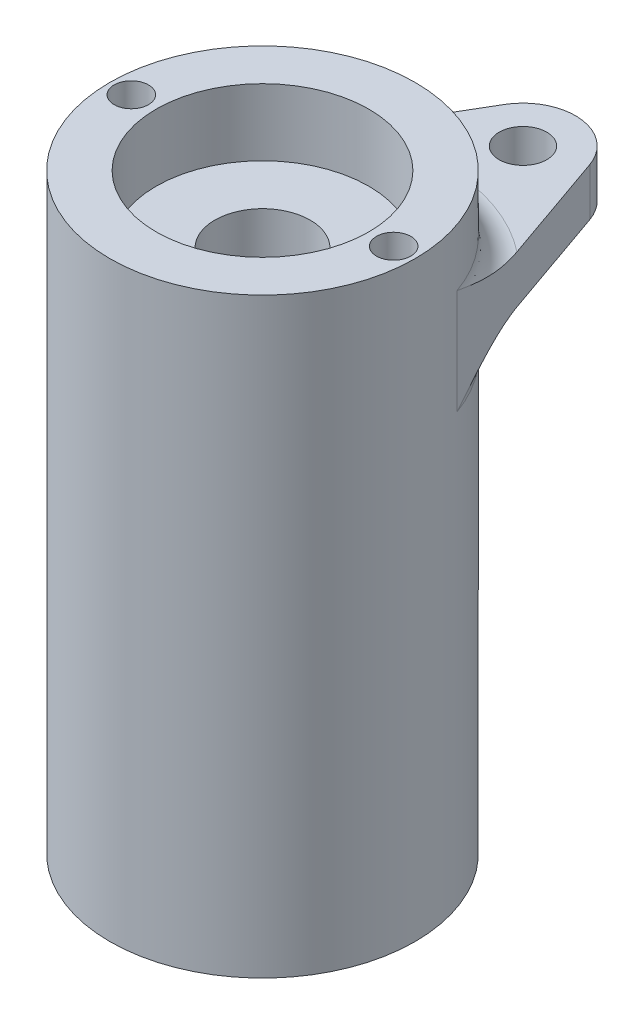
SolidWorks part; units mm, degrees
ref_plane "Front Plane" through (0, 0, 0) normal (0, 0, 1) x (1, 0, 0)
ref_plane "Top Plane" through (0, 0, 0) normal (0, 1, 0) x (1, 0, 0)
ref_plane "Right Plane" through (0, 0, 0) normal (1, 0, 0) x (0, 0, -1)
sketch "Sketch1" plane through (0, 0, 0) normal (0, 1, 0) x (1, 0, 0)
  circle A0 centre (0, 0) radius 16
  circle A1 centre (0, 0) radius 5
  dimension "D1" = 32
  dimension "D2" = 10
extrude "Boss-Extrude1" add sketch "Sketch1" along normal blind 62
sketch "Sketch2" plane through (0, 62, 0) normal (0, 1, 0) x (1, 0, 0)
  circle A0 centre (0, 0) radius 11.15
  dimension "D1" = 22.3
extrude "Cut-Extrude1" cut sketch "Sketch2" against normal blind 7
sketch "Sketch3" plane through (0, 0, 0) normal (0, -1, 0) x (1, 0, 0)
  circle A0 centre (0, 0) radius 11.15
  dimension "D1" = 22.3
extrude "Cut-Extrude2" cut sketch "Sketch3" against normal blind 7
ref_plane "Plane1" through (0, 53, 0) normal (0, 1, 0) x (1, 0, 0)
sketch "Sketch4" plane through (0, 53, 0) normal (0, 1, 0) x (1, 0, 0)
  line L0 (0, 25) -> (0, 0) construction
  line L1 (0, 0) -> (2.4222, 24.8824) construction
  line L2 (-2.3219, 27.6651) -> (-13.801, 8.0952)
  line L3 (7.6139, 26.6979) -> (15.1032, 5.2815)
  circle A0 centre (0, 0) radius 25 construction
  circle A1 centre (2.4222, 24.8824) radius 5.5
  circle A2 centre (2.4222, 24.8824) radius 2.5
  circle A3 centre (0, 0) radius 16 construction
  circle A4 centre (0, 0) radius 16
  dimension "D1" = 50
  dimension "D2" = 11
  dimension "D4" = 5
  dimension "D3" = 5.56
extrude "Boss-Extrude2" add sketch "Sketch4" against normal blind 5 contours A4 L3 A1 L2 | A1 A2 region at (1.71, 53, -17.5662) region at (2.94, 53, -30.2017)
sketch "Sketch5" plane through (0, 62, 0) normal (0, 1, 0) x (1, 0, 0)
  line L0 (0, 0) -> (-16, 0) construction
  line L1 (-16, 0) -> (16, 0) construction
  circle A0 centre (0, 0) radius 16 construction
  circle A1 centre (-13.75, 0) radius 1.8
  circle A2 centre (0, 0) radius 13.75 construction
  circle A3 centre (13.75, 0) radius 1.8
  dimension "D1" = 3.6
  dimension "D2" = 27.5
extrude "Cut-Extrude3" cut sketch "Sketch5" against normal blind 6
sketch "Sketch6" plane through (0, 0, 0) normal (0, -1, 0) x (1, 0, 0)
  circle A0 centre (-13.75, 0) radius 1.8
  circle A1 centre (13.75, 0) radius 1.8
  circle A2 centre (0, 0) radius 13.75 construction
  dimension "D1" = 3.6
extrude "Cut-Extrude4" cut sketch "Sketch6" against normal blind 6
fillet "Fillet1" radius 3 2 edges at (1.5502, 53, -15.9247) (1.5502, 48, -15.9247)
